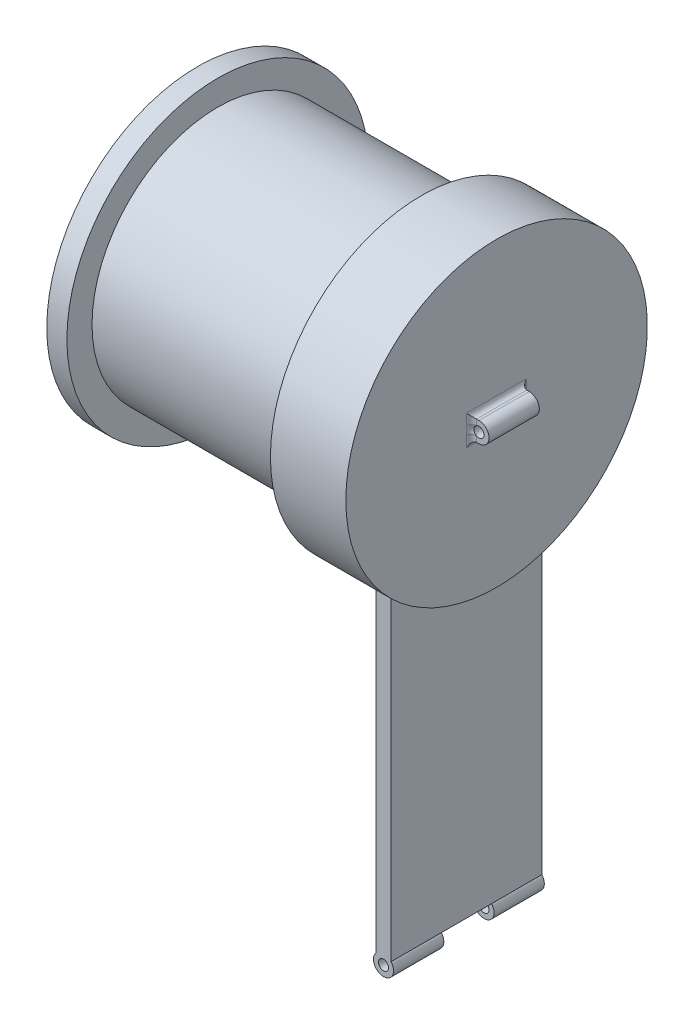
SolidWorks part; units mm, degrees
ref_plane "Front Plane" through (0, 0, 0) normal (0, 0, 1) x (1, 0, 0)
ref_plane "Top Plane" through (0, 0, 0) normal (0, 1, 0) x (1, 0, 0)
ref_plane "Right Plane" through (0, 0, 0) normal (1, 0, 0) x (0, 0, -1)
sketch "Sketch1" plane through (0, 0, 0) normal (0, 0, 1) x (1, 0, 0)
  line L0 (-15.35, 0) -> (18.4, 0) construction
  line L1 (-8.2, 0) -> (-8.2, 30)
  line L2 (-8.2, 30) -> (-4.2, 30)
  line L3 (-4.2, 30) -> (-4.2, 25)
  line L4 (-4.2, 25) -> (36.3, 25)
  line L5 (36.3, 25) -> (36.3, 30)
  line L6 (36.3, 30) -> (51.3, 30)
  line L7 (51.3, 30) -> (51.3, 0)
  line L8 (51.3, 0) -> (-8.2, 0)
  point P5 (0, 0)
  point P12 (0, 0)
  point P13 (0, 0)
  dimension "D1" = 4
  dimension "D2" = 40.5
  dimension "D3" = 30
  dimension "D4" = 25
  dimension "D5" = 15
revolve "Revolve1" add sketch "Sketch1" angle 360 about L0
sketch "Sketch2" plane through (0, 0, 0) normal (0, 0, 1) x (1, 0, 0)
  line L0 (42.3, -30) -> (42.3, -90)
  line L1 (36.3, -30) -> (51.3, -30) construction
  line L2 (42.3, -90) -> (45.3, -90)
  line L3 (45.3, -90) -> (45.3, -30)
  line L4 (45.3, -30) -> (45.3, -27.6645)
  line L5 (43.8, 30) -> (43.8, -34.1871) construction
  line L6 (51.3, 30) -> (36.3, 30) construction
  line L7 (45.3, -27.6645) -> (45.3, -23.5553)
  line L8 (42.3, -27.6645) -> (42.3, -30)
  line L9 (45.3, -23.5553) -> (42.3, -23.5553)
  line L10 (42.3, -23.5553) -> (42.3, -27.6645)
  dimension "D1" = 3
  dimension "D2" = 60
extrude "Boss-Extrude1" add sketch "Sketch2" along normal blind 15 and the other way blind 15 separate body
sketch "Sketch3" plane through (0, 0, -15) normal (0, 0, -1) x (-1, 0, 0)
  circle A0 centre (-43.8, -91.3229) radius 2
  circle A1 centre (-43.8, -91.3229) radius 1
  dimension "D1" = 4
  dimension "D2" = 2
extrude "Boss-Extrude2" add sketch "Sketch3" against normal blind 10
pattern_linear "LPattern1" count 2 spacing 20 along (0, 0, 1) of "Boss-Extrude2"
sketch "Sketch4" plane through (0, 0, 0) normal (0, 0, 1) x (1, 0, 0)
  line L0 (51.3, 0) -> (-14.483, 0) construction
  line L1 (51.3, -30) -> (51.3, 30) construction
  line L2 (51.3, -2) -> (52.8, -2)
  line L3 (52.8, 2) -> (51.3, 2)
  line L4 (51.3, 2) -> (51.3, -2)
  arc A0 (52.8, -2) -> (52.8, 2) centre (52.8, 0) ccw
  circle A1 centre (52.8, 0) radius 1
  dimension "D2" = 2
  dimension "D3" = 2
  dimension "D1" = 1.5
extrude "Boss-Extrude3" add sketch "Sketch4" along normal mid plane 10
fillet "Fillet2" radius 1 4 edges at (51.3, 0, 5) (51.3, -2, 0) (51.3, 0, -5) (51.3, 2, 0)
